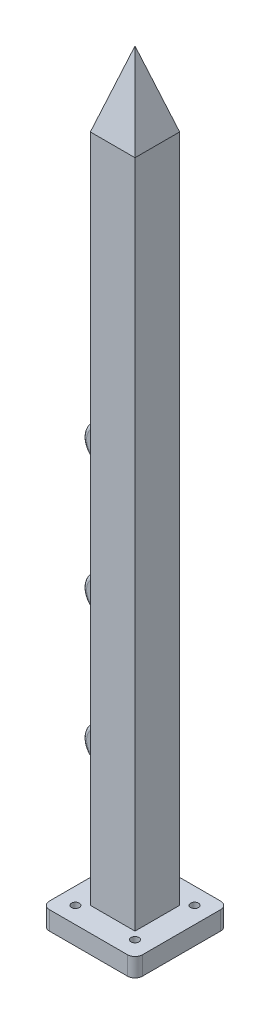
SolidWorks part; units mm, degrees
material "ABS PC"
ref_plane "Front Plane" through (0, 0, 0) normal (0, 0, 1) x (1, 0, 0)
ref_plane "Top Plane" through (0, 0, 0) normal (0, 1, 0) x (1, 0, 0)
ref_plane "Right Plane" through (0, 0, 0) normal (1, 0, 0) x (0, 0, -1)
sketch "Sketch1" plane through (0, 0, 0) normal (0, 1, 0) x (1, 0, 0)
  line L1 (0, 0) -> (25, 0)
  line L2 (0, 0) -> (0, 25)
  line L3 (0, 25) -> (25, 25)
  line L4 (25, 0) -> (25, 25)
  dimension "D1" = 25
  dimension "D2" = 25
extrude "Boss-Extrude1" add sketch "Sketch1" along normal blind 5
sketch "Sketch2" plane through (0, 5, 0) normal (0, 1, 0) x (1, 0, 0)
  line L0 (0, 0) -> (25, 0) construction
  line L1 (0, 25) -> (0, 0) construction
  line L2 (25, 0) -> (25, 25) construction
  line L3 (25, 25) -> (0, 25) construction
  circle A0 centre (4.5, 4.5) radius 1.05
  circle A1 centre (20.5, 4.5) radius 1.05
  circle A2 centre (20.5, 20.5) radius 1.05
  circle A3 centre (4.5, 20.5) radius 1.05
  dimension "D1" = 2.1
  dimension "D4" = 2.1
  dimension "D6" = 2.1
  dimension "D8" = 2.1
  dimension "D2" = 4.5
  dimension "D3" = 4.5
  dimension "D5" = 4.5
  dimension "D7" = 4.5
extrude "Cut-Extrude1" cut sketch "Sketch2" against normal blind 5
fillet "Fillet1" radius 2 4 edges at (0, 2.5, -25) (0, 2.5, 0) (25, 2.5, -25) (25, 2.5, 0)
sketch "Sketch3" plane through (0, 5, 0) normal (0, 1, 0) x (1, 0, 0)
  line L0 (2, 0) -> (23, 0) construction
  line L1 (6.5, 6.5) -> (18.5, 6.5)
  line L2 (6.5, 6.5) -> (6.5, 18.5)
  line L3 (6.5, 18.5) -> (18.5, 18.5)
  line L4 (18.5, 6.5) -> (18.5, 18.5)
  line L5 (25, 2) -> (25, 23) construction
  dimension "D1" = 12
  dimension "D2" = 6.5
  dimension "D3" = 6.5
extrude "Boss-Extrude2" add sketch "Sketch3" along normal blind 200
sketch "Sketch4" plane through (0, 205, 0) normal (0, 1, 0) x (1, 0, 0)
  line L1 (10, 15) -> (15, 15)
  line L2 (10, 15) -> (10, 10)
  line L3 (10, 10) -> (15, 10)
  line L4 (15, 15) -> (15, 10)
  line L5 (10, 15) -> (15, 10) construction
  line L6 (10, 10) -> (15, 15) construction
  point P0 (12.5, 12.5)
  dimension "D1" = 5
extrude "Cut-Extrude2" cut sketch "Sketch4" against normal blind 140
sketch "Sketch5" plane through (0, 205, 0) normal (0, 1, 0) x (1, 0, 0)
  line L1 (15, 15) -> (10, 15)
  line L2 (15, 15) -> (15, 10)
  line L3 (15, 10) -> (10, 10)
  line L4 (10, 15) -> (10, 10)
extrude "Boss-Extrude3" add sketch "Sketch5" against normal blind 20
sketch "Sketch7" plane through (18.5, 0, 0) normal (1, 0, 0) x (0, 0, -1)
  line L0 (12.5, 205) -> (18.5, 205)
  line L1 (6.5, 205) -> (18.5, 205) construction
  line L2 (18.5, 205) -> (18.5, 5) construction
  line L3 (18.5, 205) -> (18.5, 185)
  line L4 (18.5, 185) -> (12.5, 205)
  line L5 (6.5, 205) -> (6.5, 185)
  line L6 (6.5, 205) -> (6.5, 5) construction
  line L7 (6.5, 185) -> (12.5, 205)
  dimension "D1" = 20
  dimension "D2" = 20
sketch "Sketch10" plane through (6.5, 0, 0) normal (-1, 0, 0) x (0, 0, 1)
  line L0 (-6.5, 205) -> (-12.5, 205)
  line L1 (-6.5, 205) -> (-6.5, 5) construction
  line L2 (-18.5, 205) -> (-6.5, 205) construction
  line L3 (-12.5, 205) -> (-6.5, 205)
  line L4 (-6.5, 205) -> (-6.5, 185)
  line L5 (-6.5, 185) -> (-12.5, 205)
  line L6 (-12.5, 205) -> (-18.5, 205)
  line L7 (-18.5, 205) -> (-18.5, 185)
  line L8 (-18.5, 205) -> (-18.5, 5) construction
  line L9 (-18.5, 185) -> (-12.5, 205)
  line M2 (-6.5, 5) -> (-6.5, 205)
  line M3 (-6.5, 205) -> (-18.5, 205)
  line M4 (-18.5, 205) -> (-18.5, 5)
  dimension "D1" = 20
  dimension "D2" = 20
extrude "Cut-Extrude6" cut sketch "Sketch10" against normal blind 20 contours L5 M2 M3 | L9 M4 M3 region at (6.5, 198.3333, -8.5) region at (6.5, 198.3333, -16.5)
sketch "Sketch11" plane through (0, 0, -6.5) normal (0, 0, 1) x (1, 0, 0)
  line L0 (18.5, 185) -> (18.5, 205)
  line L1 (18.5, 205) -> (12.5, 205)
  line L2 (12.5, 205) -> (18.5, 185)
  line L3 (12.5, 205) -> (6.5, 205)
  line L4 (6.5, 205) -> (6.5, 185)
  line L5 (6.5, 185) -> (12.5, 205)
  dimension "D1" = 20
  dimension "D2" = 6
  dimension "D3" = 6
extrude "Cut-Extrude7" cut sketch "Sketch11" against normal blind 20 contours L4 L5 L3 | L1 L2 L0 region at (16.5, 198.3333, -6.5) region at (8.5, 198.3333, -6.5)
sketch "Sketch12" plane through (0, 0, -18.5) normal (0, 0, -1) x (-1, 0, 0)
  line L0 (-6.5, 185) -> (-6.5, 5) construction
  line L1 (-18.5, 5) -> (-6.5, 5) construction
  circle A0 centre (-6.5, 40) radius 5
  circle A1 centre (-4.5, 40) radius 1
  circle A2 centre (-6.5, 75) radius 5
  circle A3 centre (-4.5, 75) radius 1
  circle A4 centre (-6.5, 110) radius 5
  circle A5 centre (-4.5, 110) radius 1
  dimension "D1" = 10
  dimension "D2" = 2
  dimension "D5" = 10
  dimension "D6" = 2
  dimension "D11" = 10
  dimension "D12" = 2
  dimension "D13" = 2
  dimension "D3" = 35
  dimension "D4" = 35
  dimension "D7" = 2
  dimension "D8" = 2
  dimension "D9" = 70
  dimension "D10" = 70
  dimension "D14" = 105
  dimension "D15" = 105
extrude "Boss-Extrude4" add sketch "Sketch12" along normal blind 3 and the other way blind 3 from offset 6 offset against normal yes
fillet "Fillet2" radius 1 19 edges at (6.5, 40, -15.5) (6.5, 40, -9.5) (6.5, 75, -15.5) (6.5, 110, -9.5) (1.5, 40, -15.5) (6.5, 45, -12.5) (1.5, 40, -9.5) (6.5, 35, -12.5) (1.5, 75, -15.5) (6.5, 80, -12.5) (1.5, 75, -9.5) (6.5, 70, -12.5) (6.5, 75, -9.5) (1.5, 110, -9.5) (11.5, 110, -10) (1.5, 110, -15.5) (6.5, 115, -12.5) (6.5, 105, -12.5) (6.5, 110, -15.5)
